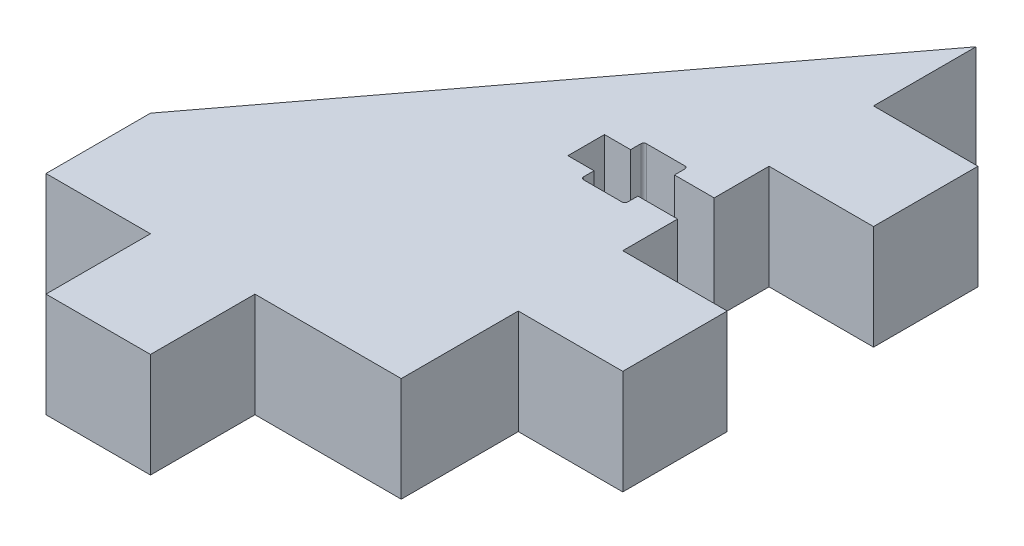
SolidWorks part; units mm, degrees
ref_plane "Front Plane" through (0, 0, 0) normal (0, 0, 1) x (1, 0, 0)
ref_plane "Top Plane" through (0, 0, 0) normal (0, 1, 0) x (1, 0, 0)
ref_plane "Right Plane" through (0, 0, 0) normal (1, 0, 0) x (0, 0, -1)
sketch "Sketch1" plane through (0, 0, 0) normal (0, 1, 0) x (1, 0, 0)
  line L0 (0, 0) -> (-14, 0)
  line L1 (-14, 0) -> (-14, -10)
  line L2 (-14, -10) -> (-24, -10)
  line L3 (-24, -10) -> (-24, 0)
  line L4 (-24, 0) -> (-34, 0)
  line L5 (-34, 0) -> (-34, 10)
  line L6 (-34, 10) -> (0, 55)
  line L7 (0, 55) -> (0, 45.2)
  line L8 (0, 45.2) -> (10, 45.2)
  line L9 (10, 45.2) -> (10, 35.2)
  line L10 (10, 35.2) -> (0, 35.2)
  line L11 (0, 35.2) -> (0, 21.2)
  line L12 (-24, 0) -> (-14, 0) construction
  line L13 (-19, 0) -> (-19, -10) construction
  line L14 (0, 16.2) -> (0, 11.2) construction
  line L15 (5, 11.2) -> (5, 21.2) construction
  line L24 (0, 21.2) -> (10, 21.2)
  line L25 (10, 21.2) -> (10, 11.2)
  line L26 (10, 11.2) -> (0, 11.2)
  line L27 (0, 11.2) -> (0, 0)
  line L32 (10, 40.2) -> (0, 40.2) construction
  line L33 (0, 40.2) -> (0, 35.2) construction
  line L34 (10, 16.2) -> (0, 16.2) construction
  line L35 (0, 16.2) -> (0, 21.2) construction
  dimension "D2" = 10
  dimension "D3" = 10
  dimension "D7" = 10
  dimension "D8" = 10
  dimension "D10" = 10
  dimension "D11" = 10
  dimension "D12" = 10
  dimension "D9" = 55
  dimension "D5" = 16.2
  dimension "D13" = 24
  dimension "D4" = 24
  dimension "D6" = 24
extrude "Boss-Extrude1" add sketch "Sketch1" along normal blind 10
sketch "Sketch2" [suppressed] plane through (0, 8, 0) normal (0, 1, 0) x (1, 0, 0)
  line L0 (0, 29.9) -> (0, 25.9) construction
  line L1 (0, 27.9) -> (-7.2, 27.9) construction
  line L2 (-7.2, 25.9) -> (-7.2, 29.9) construction
  line L3 (7.5, 36.4) -> (7.5, 20.4) construction
  line L4 (0, 36.4) -> (7.5, 36.4) construction
  line L5 (0, 27.9) -> (7.5, 27.9) construction
sketch "Sketch3" plane through (0, 10, 0) normal (0, 1, 0) x (1, 0, 0)
  line L0 (0, 28.2) -> (-10.5, 28.2) construction
  line L1 (0, 21.2) -> (0, 35.2) construction
  line L2 (-10.5, 29.95) -> (-8, 29.95)
  line L3 (-8, 29.95) -> (-8, 30.95)
  line L4 (-7.75, 31.2) -> (-4.05, 31.2)
  line L5 (-3.8, 30.95) -> (-3.8, 29.95)
  line L6 (-3.8, 29.95) -> (0, 29.95)
  line L7 (0, 29.95) -> (0, 26.45)
  line L8 (-10.5, 29.95) -> (-10.5, 26.45)
  line L9 (-3.8, 26.45) -> (0, 26.45)
  line L10 (-3.8, 25.45) -> (-3.8, 26.45)
  line L11 (-7.75, 25.2) -> (-4.05, 25.2)
  line L12 (-8, 26.45) -> (-8, 25.45)
  line L13 (-10.5, 26.45) -> (-8, 26.45)
  arc A0 (-8, 30.95) -> (-7.75, 31.2) centre (-7.75, 30.95) cw
  arc A1 (-4.05, 31.2) -> (-3.8, 30.95) centre (-4.05, 30.95) cw
  arc A2 (-4.05, 25.2) -> (-3.8, 25.45) centre (-4.05, 25.45) ccw
  arc A3 (-8, 25.45) -> (-7.75, 25.2) centre (-7.75, 25.45) ccw
  point P12 (-8, 31.2)
  point P15 (-3.8, 31.2)
  point P26 (-3.8, 25.2)
  point P27 (-8, 25.2)
  dimension "D7" = 0.25
  dimension "D1" = 10.5
  dimension "D3" = 1.75
  dimension "D2" = 8
  dimension "D4" = 4.2
  dimension "D5" = 3
  dimension "D6" = 1.75
extrude "Cut-Extrude1" cut sketch "Sketch3" against normal through all
equation "\"Y-ROD-SPACING\"=75"
equation "\"Y-BED-OFFSET\"=2"
equation "\"Y-BED-ROD-INSET\"=3.5"
equation "\"T-SLOT-NUT-FILLET-RADIUS\"=0.25"
equation "\"T-SLOT-SCREW-SHAFT-RADIUS\"=1.75"
equation "\"T-SLOT-SCREW-SHAFT-CUTOUT-LENGTH\"=10.5"
equation "\"T-SLOT-NUT-DEPTH\"=4.2"
equation "\"T-SLOT-NUT-WIDTH\"=3"
equation "\"T-SLOT-NUT-END-DISTANCE\"=8"
equation "\"ACRYLIC-TAB-CUTOUT-SIZE\"=\"ACRYLIC-THICKNESS\"+\"ACRYLIC-TAB-TOLERANCE\"*2"
equation "\"ACRYLIC-TAB-WIDTH\"=\"ACRYLIC-THICKNESS\""
equation "\"ACRYLIC-M3-HOLE\"=3.2"
equation "\"SMOOTHROD-CAP-SCREW-DISTANCE\"=20"
equation "\"FRAME-WIDTH-INNER\"=370"
equation "\"NEMA17-HOLE-SPACING\"=31"
equation "\"NEMA17-CENTRAL-CUTOUT\"=22.5"
equation "\"D3@Sketch1\"=\"ACRYLIC-TAB-WIDTH\""
equation "\"D12@Sketch1\"=\"ACRYLIC-TAB-WIDTH\""
equation "\"D2@Sketch1\"=\"ACRYLIC-TAB-WIDTH\""
equation "\"D11@Sketch1\"=\"ACRYLIC-TAB-WIDTH\""
equation "\"D1@Sketch1\"=\"ACRYLIC-TAB-WIDTH\""
equation "\"D10@Sketch1\"=\"ACRYLIC-TAB-WIDTH\""
equation "\"Z-BRACKET-REACH\"=55"
equation "\"D9@Sketch1\"=\"Z-BRACKET-REACH\""
equation "\"D6@Sketch3\"=\"T-SLOT-SCREW-SHAFT-RADIUS\""
equation "\"D3@Sketch3\"=\"T-SLOT-SCREW-SHAFT-RADIUS\""
equation "\"D4@Sketch3\"=\"T-SLOT-NUT-DEPTH\""
equation "\"D7@Sketch3\"=\"T-SLOT-NUT-FILLET-RADIUS\""
equation "\"D1@Sketch3\"=\"T-SLOT-SCREW-SHAFT-CUTOUT-LENGTH\""
equation "\"D5@Sketch3\"=\"T-SLOT-NUT-WIDTH\""
equation "\"D2@Sketch3\"=\"T-SLOT-NUT-END-DISTANCE\""
equation "\"X-ROD-SPACING\"=45"
equation "\"Z-ROD-SPACING\"=17.5"
equation "\"ACRYLIC-THICKNESS\"=10"
equation "\"ACRYLIC-THICKNESS2\"=4.5"
equation "\"TOP-BRACKET-SPACING\"=40"
equation "\"SMOOTHROD-X-LENGTH\"=350"
equation "\"SMOOTHROD-Y-LENGTH\"=350"
equation "\"SMOOTHROD-Z-LENGTH\"=350"
equation "\"SMOOTHROD-TIGHTENING-HEADROOM\"=1"
equation "\"LEADSCREW-Z-LENGTH\"=300"
equation "\"SCREW-LENGTH-FRAME\"=\"ACRYLIC-THICKNESS\" + 10"
equation "\"SCREW-HEAD-RADIUS\"=6"
equation "\"PRINTED-X-SMOOTHROD-DIAMETER\"=8.2"
equation "\"PRINTED-X-SMOOTHROD-CUTOUT\"=10"
equation "\"PRINTED-X-BASE-HEIGHT\"=10"
equation "\"PRINTED-LM8UU-CUTOUT-SIZE\"=16"
equation "\"PRINTED-LM8UU-CUTOUT-LENGTH\"=24.5"
equation "\"PRINTED-X-IDLER-HEIGHT\"=16"
equation "\"PSU-MOUNTING-WIDTH\"=95"
equation "\"PSU-MOUNTING-HEIGHT\"=177"
equation "\"D1@Boss-Extrude1\"=\"ACRYLIC-THICKNESS\""
